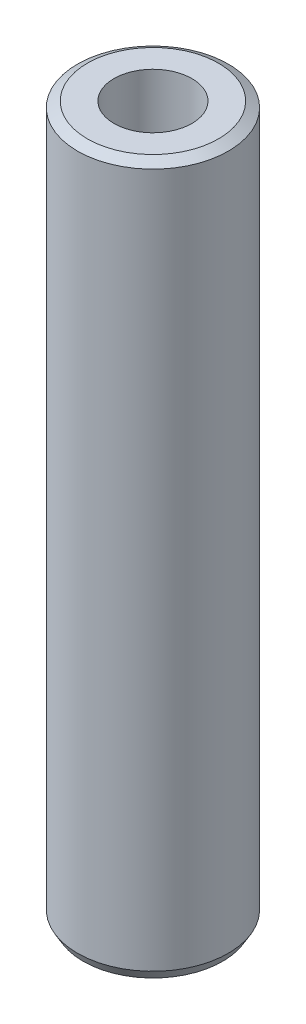
SolidWorks part; units mm, degrees
ref_plane "Front Plane" through (0, 0, 0) normal (0, 0, 1) x (1, 0, 0)
ref_plane "Top Plane" through (0, 0, 0) normal (0, 1, 0) x (1, 0, 0)
ref_plane "Right Plane" through (0, 0, 0) normal (1, 0, 0) x (0, 0, -1)
sketch "Sketch1" plane through (0, 0, 0) normal (0, 1, 0) x (1, 0, 0)
  circle A0 centre (0, 0) radius 45
  dimension "SHAFT_OD" = 90
extrude "Boss-Extrude1" add sketch "Sketch1" along normal blind 423.6752
sketch "Sketch2" plane through (0, 0, 0) normal (0, 1, 0) x (1, 0, 0)
  circle A0 centre (0, 0) radius 23.2345
  dimension "BORE_D" = 46.4689
extrude "Cut-Extrude1" cut sketch "Sketch2" along normal through all
chamfer "Chamfer1" distance 3.3933 angle 60 2 edges at (0, 423.6752, 45) (0, 0, 45) first distance on face at (0, 423.6752, 45) first distance on face at (0, 0, 23.2345)
